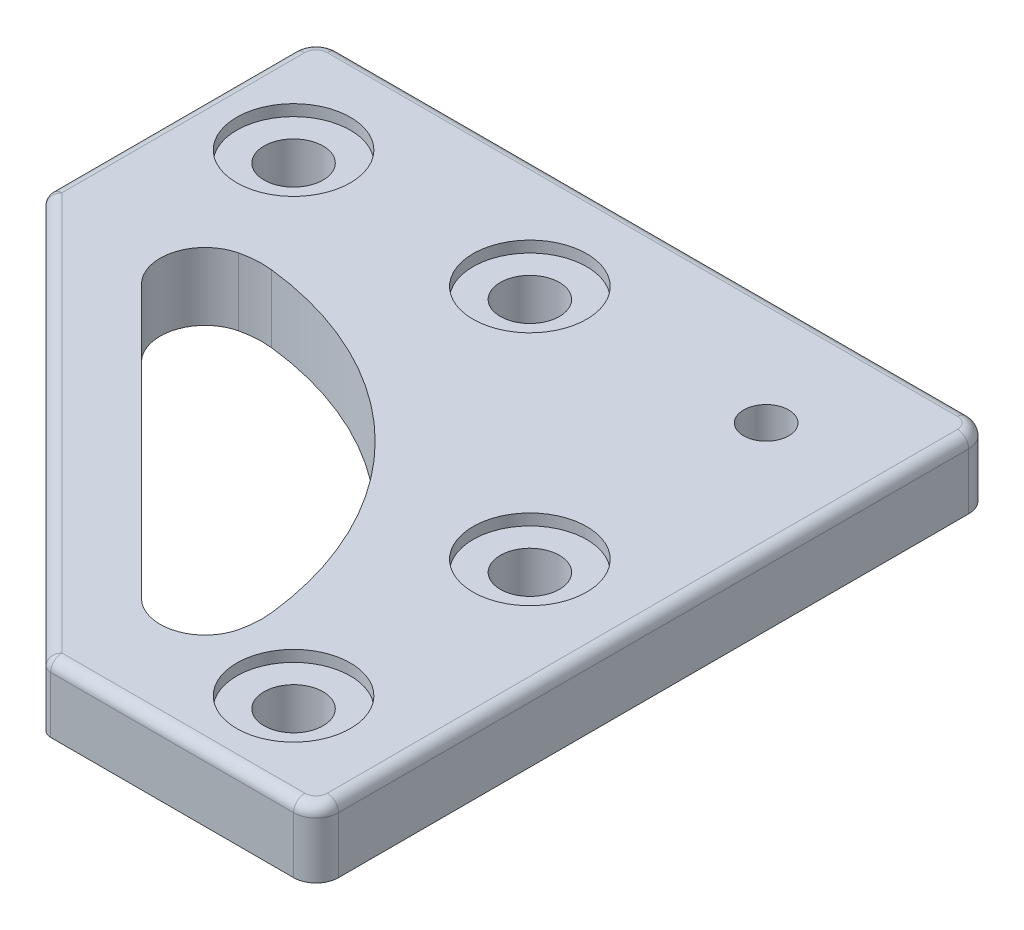
SolidWorks part; units mm, degrees
ref_plane "Front Plane" through (0, 0, 0) normal (0, 0, 1) x (1, 0, 0)
ref_plane "Top Plane" through (0, 0, 0) normal (0, 1, 0) x (1, 0, 0)
ref_plane "Right Plane" through (0, 0, 0) normal (1, 0, 0) x (0, 0, -1)
sketch "Sketch1" plane through (0, 0, 0) normal (0, 1, 0) x (1, 0, 0)
  line L0 (-34.8284, 10) -> (7.1716, 10) construction
  line L2 (0, 0) -> (0, -34.3431)
  line L3 (-0.8284, -40) -> (15.1716, -40)
  line L4 (17.1716, -10.1754) -> (17.1716, -38)
  line L5 (0, 0) -> (-34.3431, 0)
  line L6 (17.1716, -10.1754) -> (17.1716, 18)
  line L7 (15.1716, 20) -> (-40.8284, 20)
  line L8 (-42.8284, 2) -> (-42.8284, 18)
  line L9 (7.1716, -32) -> (7.1716, -11) construction
  line L10 (-42.8284, 2) -> (-42.8284, -4)
  line L11 (-42.8284, -4) -> (-6.8284, -40)
  line L12 (-6.8284, -40) -> (-0.8284, -40)
  line L13 (-34.3431, 0) -> (-34.3431, -4)
  line L14 (-34.3431, -4) -> (-4, -34.3431)
  line L15 (-4, -34.3431) -> (0, -34.3431)
  circle A0 centre (-34.8284, 10) radius 2.625
  circle A1 centre (-13.8284, 10) radius 2.625
  circle A4 centre (7.1716, -32) radius 2.625
  circle A5 centre (7.1716, 10) radius 2.625
  circle A6 centre (7.1716, -11) radius 2.625
  arc A8 (17.1716, -38) -> (15.1716, -40) centre (15.1716, -38) cw
  arc A10 (17.1716, 18) -> (15.1716, 20) centre (15.1716, 18) ccw
  arc A12 (-40.8284, 20) -> (-42.8284, 18) centre (-40.8284, 18) ccw
  point P12 (-42.8284, 10)
  point P30 (-42.8284, 0)
  point P33 (-42.8284, 20)
  point P36 (-24.8284, -22)
  dimension "D7" = 5.25
  dimension "D8" = 2
  dimension "D1" = 20
  dimension "D2" = 40
  dimension "D3" = 10
  dimension "D4" = 8
  dimension "D5" = 21
  dimension "D6" = 21
  dimension "D9" = 21
  dimension "D10" = 4
  dimension "D11" = 4
  dimension "D12" = 6
  dimension "D13" = 10
extrude "Boss-Extrude1" add sketch "Sketch1" along normal blind 6
fillet "Fillet1" radius 30 1 edges at (0, 3, 0)
sketch "Sketch2" plane through (0, 6, 0) normal (0, 1, 0) x (1, 0, 0)
  circle A0 centre (-34.8284, 10) radius 5.05
  circle A1 centre (-13.8284, 10) radius 5.05
  circle A2 centre (7.1716, 10) radius 5.05
  circle A3 centre (7.1716, -11) radius 5.05
  circle A4 centre (7.1716, -32) radius 5.05
  circle A5 centre (-34.8284, 10) radius 2.625 construction
  circle A6 centre (-13.8284, 10) radius 2.625 construction
  circle A7 centre (7.1716, 10) radius 2.625 construction
  circle A8 centre (7.1716, -11) radius 2.625 construction
  circle A9 centre (7.1716, -32) radius 2.625 construction
  dimension "D1" = 10.1
extrude "Cut-Extrude1" cut sketch "Sketch2" against normal blind 1
fillet "Fillet3" radius 1 7 edges at (16.5858, 6, -19.4142) (17.1716, 6, 10) (16.5858, 6, 39.4142) (4.1716, 6, 40) (-42.8284, 6, -7) (-42.2426, 6, -19.4142) (-12.8284, 6, -20)
sketch "Sketch3" plane through (0, 6, 0) normal (0, 1, 0) x (1, 0, 0)
  circle A0 centre (7.1716, 10) radius 2
  circle A1 centre (7.1716, 10) radius 5.05
  dimension "D1" = 4
extrude "Boss-Extrude2" add sketch "Sketch3" against normal blind 4
fillet "Fillet4" radius 8 2 edges at (0, 3, 34.3431) (-34.3431, 3, 0)
fillet "Fillet5" radius 4 2 edges at (-34.3431, 3, 4) (-4, 3, 34.3431)
fillet "Fillet6" radius 1 5 edges at (-42.8284, 2.5, 4) (-42.5355, 5.7071, 4.2929) (-6.8284, 2.5, 40) (-7.1213, 5.7071, 39.7071) (-24.8284, 6, 22)
